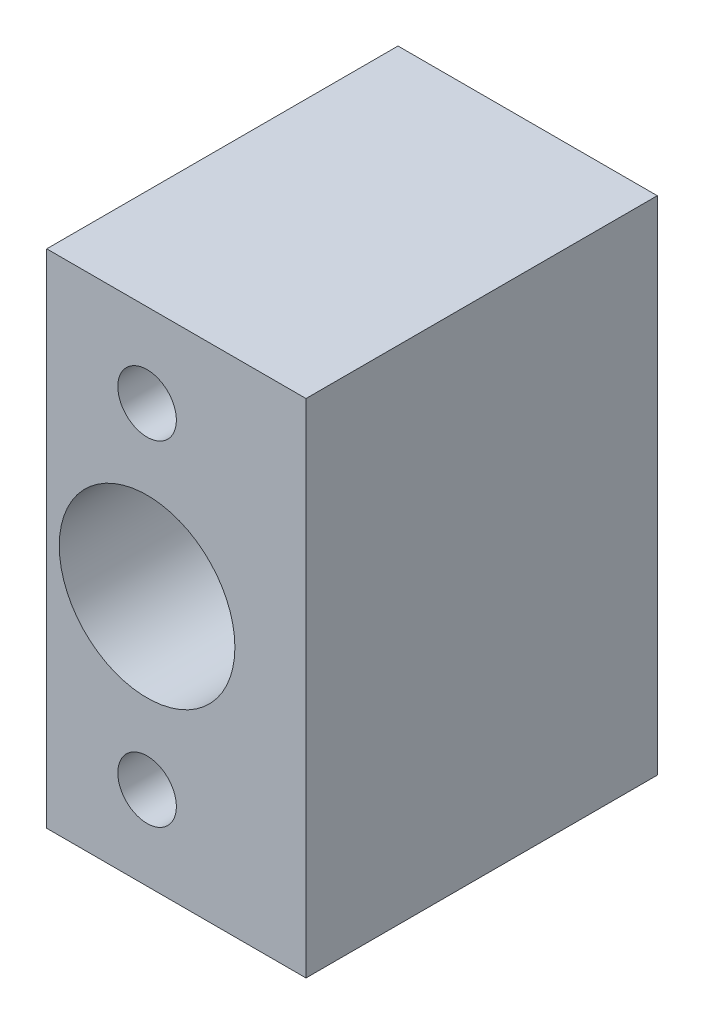
SolidWorks part; units mm, degrees
material "6061-T4 (SS)"
ref_plane "Front Plane" through (0, 0, 0) normal (0, 0, 1) x (1, 0, 0)
ref_plane "Top Plane" through (0, 0, 0) normal (0, 1, 0) x (1, 0, 0)
ref_plane "Right Plane" through (0, 0, 0) normal (1, 0, 0) x (0, 0, -1)
sketch "Sketch1" plane through (0, 0, 0) normal (0, 0, 1) x (1, 0, 0)
  line L5 (-6, 6) -> (0, 0) construction
  line L6 (0, 0) -> (6, 6) construction
  line L7 (9.5, 15) -> (-9.5, 15)
  line L8 (9.5, 15) -> (9.5, -15)
  line L9 (9.5, -15) -> (-9.5, -15)
  line L10 (-9.5, 15) -> (-9.5, -15)
  line L11 (9.5, 15) -> (-9.5, -15) construction
  line L12 (9.5, -15) -> (-9.5, 15) construction
  point P0 (0, 0)
  dimension "D1" = 19
  dimension "D4" = 30
extrude "Boss-Extrude1" add sketch "Sketch1" along normal blind 18
sketch "Sketch2" plane through (0, 0, 18) normal (0, 0, 1) x (1, 0, 0)
  circle A0 centre (0, 0) radius 5.25
  dimension "D1" = 10.5
extrude "Cut-Extrude1" cut sketch "Sketch2" against normal blind 11.5 contours A0
sketch "Sketch4" plane through (0, 0, 6.5) normal (0, 0, 1) x (1, 0, 0)
  circle A0 centre (0, 0) radius 4.8
  dimension "D1" = 9.6
extrude "Cut-Extrude3" cut sketch "Sketch4" against normal blind 1
sketch "Sketch5" plane through (0, 0, 5.5) normal (0, 0, 1) x (1, 0, 0)
  circle A0 centre (0, 0) radius 2.36
  dimension "D1" = 4.72
extrude "Cut-Extrude4" cut sketch "Sketch5" against normal blind 8 and the other way through all
sketch "Sketch6" plane through (0, 0, 0) normal (0, 0, 1) x (1, 0, 0)
  line L0 (-6, 15) -> (-6, -15)
  line L3 (9.5, 15) -> (-9.5, 15) construction
  line L4 (-9.5, -15) -> (9.5, -15) construction
  circle A0 centre (0, 0) radius 5.25 construction
  point P6 (-6, 0)
  dimension "D1" = 6
extrude "Cut-Extrude6" cut sketch "Sketch6" against normal through all and the other way through all flip side to cut
sketch "Sketch11" plane through (0, 0, 0) normal (0, 0, -1) x (-1, 0, 0)
  line L1 (6, 15) -> (-9.5, 15)
  line L2 (6, 15) -> (6, -15)
  line L3 (6, -15) -> (-9.5, -15)
  line L4 (-9.5, 15) -> (-9.5, -15)
extrude "Boss-Extrude5" add sketch "Sketch11" along normal blind 5
sketch "Sketch12" plane through (0, 0, -5) normal (0, 0, -1) x (-1, 0, 0)
  circle A0 centre (0, 0) radius 4
  dimension "D1" = 8
extrude "Cut-Extrude8" cut sketch "Sketch12" against normal blind 5
sketch "Sketch13" plane through (0, 0, -5) normal (0, 0, -1) x (-1, 0, 0)
  line L2 (6, 15) -> (-9.5, 15) construction
  line L3 (0, 15) -> (0, -15) construction
  line L4 (-9.5, -15) -> (6, -15) construction
  circle A1 centre (0, -10) radius 1.75
  circle A2 centre (0, 10) radius 1.75
  point P0 (0, 5)
  point P4 (0, -5)
  point P6 (0, 0)
  dimension "D3" = 3.5
  dimension "D4" = 10
  dimension "D1" = 5
  dimension "D2" = 5
extrude "Cut-Extrude9" cut sketch "Sketch13" against normal through all
sketch "Sketch14" plane through (0, 0, 5.5) normal (0, 0, 1) x (1, 0, 0)
  circle A0 centre (0, 0) radius 3
  dimension "D1" = 6
extrude "Cut-Extrude10" cut sketch "Sketch14" against normal blind 1
sketch "Sketch15" plane through (0, -15, 0) normal (0, -1, 0) x (1, 0, 0)
  line L1 (-6, -5) -> (9.5, -5) construction
  line L2 (-6, -5) -> (-6, 16) construction
  line L3 (-6, 16) -> (9.5, 16)
  line L4 (9.5, -5) -> (9.5, 16) construction
  line L5 (9.5, 18) -> (9.5, -5) construction
  line L6 (-6, 16) -> (9.5, 16)
  line L7 (-6, 16) -> (-6, 17) construction
  line L8 (-6, 17) -> (9.5, 17) construction
  line L9 (9.5, 16) -> (9.5, 17) construction
  line L11 (-6, 18) -> (9.5, 18)
  line L12 (-6, 18) -> (-6, 16)
  line L13 (-6, 16) -> (9.5, 16)
  line L14 (9.5, 18) -> (9.5, 16)
  line M5 (9.5, 18) -> (-6, 18)
  line M6 (-6, 18) -> (-6, -5)
  line M8 (9.5, -5) -> (9.5, 18)
  dimension "D1" = 21
  dimension "D2" = 1
extrude "Cut-Extrude11" cut sketch "Sketch15" against normal blind 41 contours L3 M6 M8 M5 region at (1.75, -15, 17)
ref_axis "Axis1" through (-6.0963, -15.1864, -5.1304) along (0.3898, 0.7544, 0.5281)
ref_plane "Plane2" through (-6, -15, -5) normal (0.3898, 0.7544, 0.5281) x (0.9209, -0.3193, -0.2235)
sketch "Sketch17" plane through (-6, -15, -5) normal (0.3898, 0.7544, 0.5281) x (0.9209, -0.3193, -0.2235)
  circle A0 centre (0, 0) radius 5
  dimension "D1" = 10
extrude "Cut-Extrude12" cut sketch "Sketch17" along normal blind 2
sketch "Sketch18" plane through (-5.5724, -10.7852, -7.5496) normal (-0.3898, -0.7544, -0.5281) x (0.9209, -0.3193, -0.2235)
  point P0 (0.3822, 4.5058)
sketch "Sketch20" plane through (0, 0, -5) normal (0, 0, -1) x (-1, 0, 0)
  circle A0 centre (0, 10) radius 3.81
  circle A1 centre (0, -10) radius 3.81
  circle A2 centre (0, -10) radius 1.75 construction
  dimension "D1" = 7.62
extrude "Cut-Extrude13" cut sketch "Sketch20" against normal blind 9
